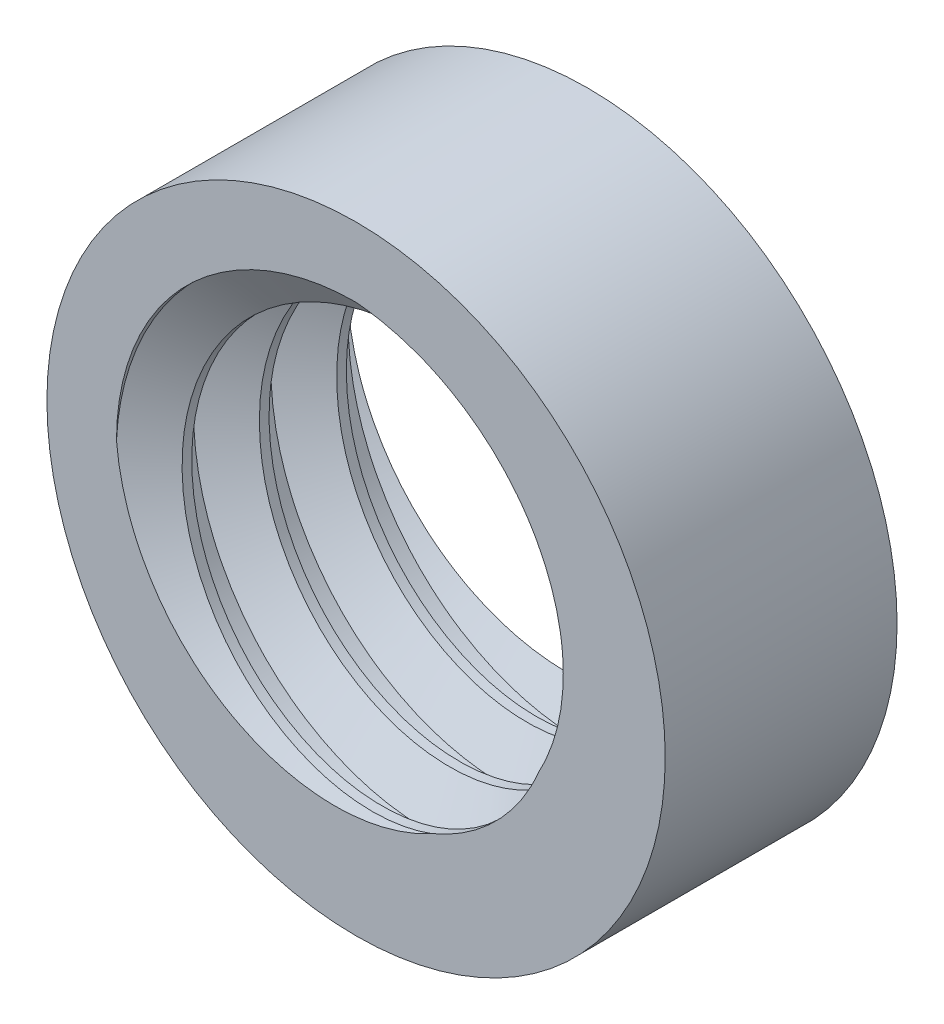
SolidWorks part; units mm, degrees
material "사용자정의 플라스틱"
ref_plane "정면" through (0, 0, 0) normal (0, 0, 1) x (1, 0, 0)
ref_plane "윗면" through (0, 0, 0) normal (0, 1, 0) x (1, 0, 0)
ref_plane "우측면" through (0, 0, 0) normal (1, 0, 0) x (0, 0, -1)
sketch "스케치1" plane through (0, 0, 0) normal (0, 0, 1) x (1, 0, 0)
  circle A0 centre (0, 0) radius 15.5
  circle A1 centre (0, 0) radius 20
  dimension "D1" = 40
  dimension "D2" = 31
extrude "보스-돌출1" add sketch "스케치1" along normal blind 15
thread "나사산1" pitch 5 method extrude trim with start face yes trim with end face yes profile "나사산 프로파일1" start angle 0, offset 10, length 25, pitch 5, diameter 31
ref_plane "평면1" through (-15.5, 0, 25) normal (0, 1, 0) x (1, 0, 0)
sketch "나사산 프로파일1" plane through (-15.5, 0, 25) normal (0, 1, 0) x (1, 0, 0)
  line L0 (0, 0) -> (0, 5) construction
  line L1 (0, 0) -> (2.7063, 1.5625)
  line L2 (2.7063, 1.5625) -> (2.7063, 2.1875)
  line L3 (2.7063, 2.1875) -> (0, 3.75)
  line L4 (2.7063, 1.875) -> (0, 1.875) construction
  line L11 (0, 0) -> (0, 3.75)
  point P2 (0, 0)
  dimension "Pitch" = 5
  dimension "Profile_Angle" = 60
  dimension "Profile_Land" = 0.625
  dimension "Profile_Height" = 2.7063
